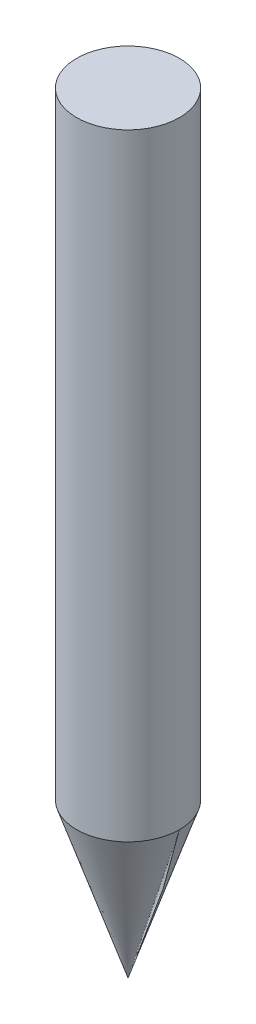
SolidWorks part; units mm, degrees
material "Brass"
ref_plane "Front Plane" through (0, 0, 0) normal (0, 0, 1) x (1, 0, 0)
ref_plane "Top Plane" through (0, 0, 0) normal (0, 1, 0) x (1, 0, 0)
ref_plane "Right Plane" through (0, 0, 0) normal (1, 0, 0) x (0, 0, -1)
sketch "Sketch1" plane through (0, 0, 0) normal (0, 0, 1) x (1, 0, 0)
  line L0 (0, 0) -> (0, 60) construction
  line L1 (0, 0) -> (4, 12)
  line L2 (4, 12) -> (4, 60)
  line L3 (4, 60) -> (0, 60)
  line L4 (0, 60) -> (0, 0)
revolve "Revolve1" add sketch "Sketch1" angle 360 about L0
